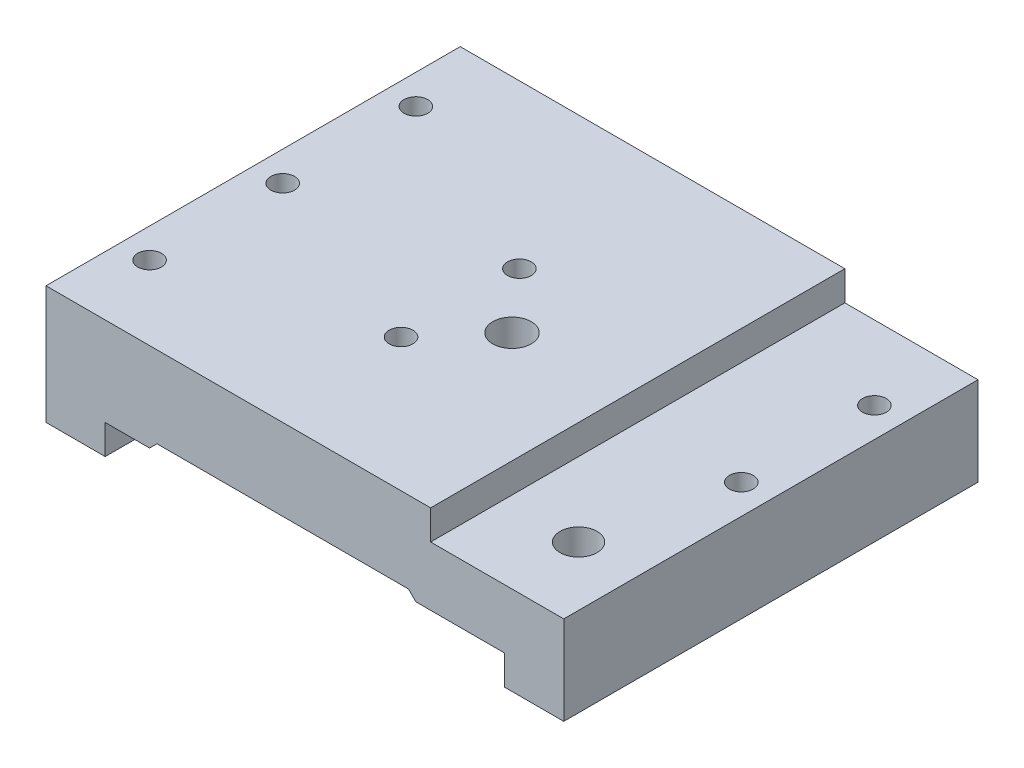
SolidWorks part; units mm, degrees
material "6061 Alloy"
ref_plane "Front Plane" through (0, 0, 0) normal (0, 0, 1) x (1, 0, 0)
ref_plane "Top Plane" through (0, 0, 0) normal (0, 1, 0) x (1, 0, 0)
ref_plane "Right Plane" through (0, 0, 0) normal (1, 0, 0) x (0, 0, -1)
sketch "Sketch1" plane through (0, 0, 0) normal (0, 1, 0) x (1, 0, 0)
  line L1 (55.5625, -44.45) -> (-55.5625, -44.45)
  line L2 (55.5625, -44.45) -> (55.5625, 44.45)
  line L3 (55.5625, 44.45) -> (-55.5625, 44.45)
  line L4 (-55.5625, -44.45) -> (-55.5625, 44.45)
  line L5 (55.5625, -44.45) -> (-55.5625, 44.45) construction
  line L6 (55.5625, 44.45) -> (-55.5625, -44.45) construction
  point P0 (0, 0)
  dimension "D1" = 111.125
  dimension "D2" = 88.9
extrude "Boss-Extrude1" add sketch "Sketch1" along normal blind 25.4
sketch "Sketch2" plane through (0, 0, 44.45) normal (0, 0, 1) x (1, 0, 0)
  line L0 (-42.8625, 0) -> (-42.8625, 6.35)
  line L1 (55.5625, 25.4) -> (26.9875, 25.4)
  line L2 (55.5625, 25.4) -> (55.5625, 19.05)
  line L3 (55.5625, 19.05) -> (26.9875, 19.05)
  line L4 (26.9875, 25.4) -> (26.9875, 19.05)
  line L5 (-55.5625, 0) -> (55.5625, 0) construction
  line L6 (-42.8625, 6.35) -> (-33.3375, 6.35)
  line L7 (-33.3375, 6.35) -> (-31.75, 7.9375)
  line L8 (-31.75, 7.9375) -> (22.225, 7.9375)
  line L9 (22.225, 7.9375) -> (23.8125, 6.35)
  line L10 (23.8125, 6.35) -> (42.8625, 6.35)
  line L11 (42.8625, 6.35) -> (42.8625, 0)
  line L12 (55.5625, 25.4) -> (55.5625, 0) construction
  line L13 (-55.5625, 25.4) -> (-55.5625, 0) construction
  line L14 (-42.8625, 0) -> (42.8625, 0)
  dimension "D1" = 6.35
  dimension "D3" = 12.7
  dimension "D4" = 12.7
  dimension "D5" = 19.05
  dimension "D6" = 1.5875
  dimension "D7" = 9.525
  dimension "D8" = 6.35
  dimension "D9" = 45
  dimension "D10" = 45
  dimension "D11" = 82.55
extrude "Cut-Extrude1" cut sketch "Sketch2" against normal through all
sketch "Sketch3" plane through (0, 7.9375, 0) normal (0, -1, 0) x (1, 0, 0)
  line L1 (-55.5625, -44.45) -> (-55.5625, 44.45) construction
  circle A0 centre (3.175, 3.175) radius 4.1326
  point P3 (-19.3796, 3.175)
  dimension "D1" = 58.7375
extrude "Cut-Extrude2" cut sketch "Sketch3" against normal through all
hole_wizard "1/4-20 Tapped Hole1" positions "Sketch4" profile "Sketch5" tap size "1/4-20" standard "ANSI Inch"
sketch "Sketch4" plane through (0, 0, 0) normal (0, -1, 0) x (-1, 0, 0)
  point P0 (49.2125, -28.575)
  point P3 (49.2125, 0)
  point P6 (49.2125, 28.575)
  point P9 (-49.2125, 28.575)
  point P12 (-49.2125, 0)
cosmetic thread "Hole Thread1" parameters "D1"=25.4, "D2"=6.35
cosmetic thread "Hole Thread2" parameters "D1"=25.4, "D2"=6.35
cosmetic thread "Hole Thread3" parameters "D1"=25.4, "D2"=6.35
cosmetic thread "Hole Thread4" parameters "D1"=25.4, "D2"=6.35
cosmetic thread "Hole Thread5" parameters "D1"=25.4, "D2"=6.35
sketch "Sketch5" plane through (-49.2125, 0, 28.575) normal (1, 0, 0) x (0, 0, -1)
  line L0 (0, 0) -> (0, 30.7438)
  line L1 (0, 30.7438) -> (2.5527, 29.21)
  line L2 (2.5527, 29.21) -> (2.5527, 0)
  line L5 (2.5527, 0) -> (0, 0)
  line L10 (0, 30.7438) -> (-2.5527, 29.21) construction
  line L11 (0, -6.35) -> (0, 107.95) construction
  dimension "Tap Drill Dia." = 5.1054
  dimension "Tap Drill Depth" = 29.21
  dimension "Drill Angle" = 118
hole_wizard "3/8-16 Tapped Hole1" positions "Sketch6" profile "Sketch7" tap size "3/8-16" standard "ANSI Inch"
sketch "Sketch6" plane through (0, 0, 0) normal (0, -1, 0) x (-1, 0, 0)
  point P0 (-42.8625, -28.575)
sketch "Sketch7" plane through (42.8625, 0, 28.575) normal (1, 0, 0) x (0, 0, -1)
  line L0 (0, 0) -> (0, 26.1972)
  line L1 (0, 26.1972) -> (3.9687, 23.8125)
  line L2 (3.9687, 23.8125) -> (3.9687, 0)
  line L5 (3.9687, 0) -> (0, 0)
  line L10 (0, 26.1972) -> (-3.9688, 23.8125) construction
  line L11 (0, -6.35) -> (0, 107.95) construction
  dimension "Tap Drill Dia." = 7.9375
  dimension "Tap Drill Depth" = 23.8125
  dimension "Drill Angle" = 118
cosmetic thread "Hole Thread6" parameters "D1"=19.05, "D2"=9.525
hole_wizard "1/4-20 Tapped Hole2" positions "Sketch8" profile "Sketch9" tap size "1/4-20" standard "ANSI Inch"
sketch "Sketch8" plane through (0, 25.4, 0) normal (0, 1, 0) x (1, 0, 0)
  point P0 (-7.9375, -15.875)
  point P3 (-7.9375, 9.525)
sketch "Sketch9" plane through (-7.9375, 25.4, 15.875) normal (1, 0, 0) x (0, 0, 1)
  line L0 (0, 0) -> (0, 11.6938)
  line L1 (0, 11.6938) -> (2.5527, 10.16)
  line L2 (2.5527, 10.16) -> (2.5527, 0)
  line L5 (2.5527, 0) -> (0, 0)
  line L10 (0, 11.6938) -> (-2.5527, 10.16) construction
  line L11 (0, -6.35) -> (0, 107.95) construction
  dimension "Tap Drill Dia." = 5.1054
  dimension "Tap Drill Depth" = 10.16
  dimension "Drill Angle" = 118
cosmetic thread "Hole Thread7" parameters "D1"=6.35, "D2"=6.35
cosmetic thread "Hole Thread8" parameters "D1"=6.35, "D2"=6.35
